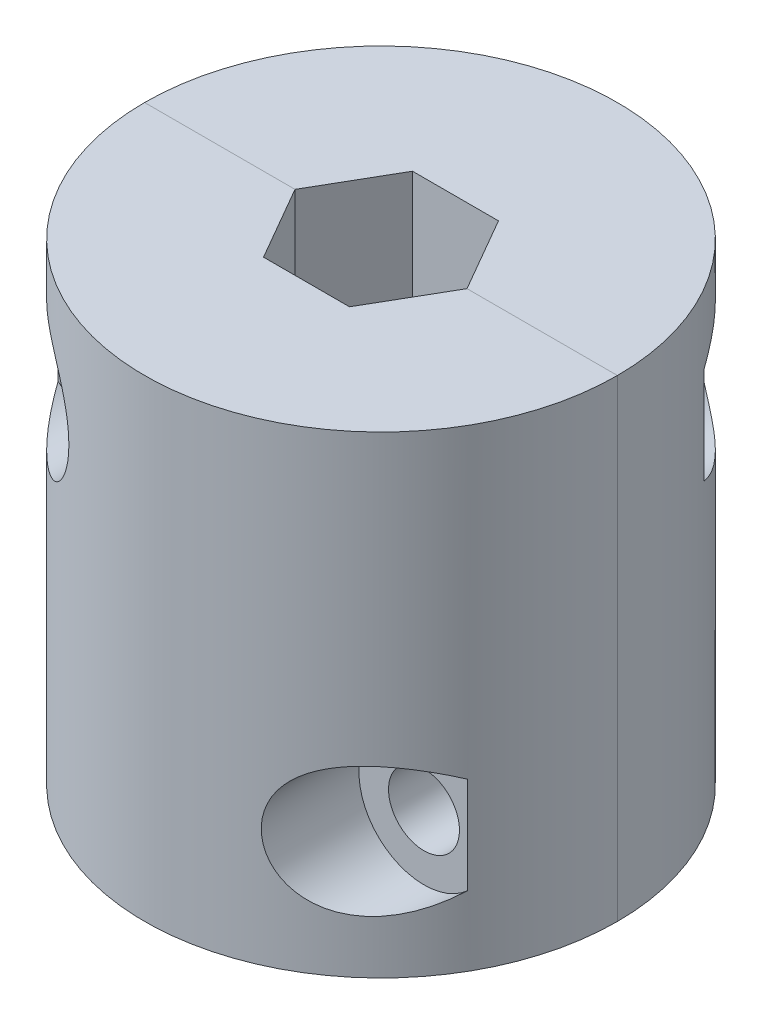
SolidWorks part; units mm, degrees
ref_plane "Front Plane" through (0, 0, 0) normal (0, 0, 1) x (1, 0, 0)
ref_plane "Top Plane" through (0, 0, 0) normal (0, 1, 0) x (1, 0, 0)
ref_plane "Right Plane" through (0, 0, 0) normal (1, 0, 0) x (0, 0, -1)
sketch "Sketch1" plane through (0, 0, 0) normal (0, 1, 0) x (1, 0, 0)
  line L0 (3.6373, 0) -> (10, 0)
  line L1 (-1.8187, -3.15) -> (1.8187, -3.15)
  line L2 (1.8187, -3.15) -> (3.6373, 0)
  line L3 (3.6373, 0) -> (1.8187, 3.15)
  line L4 (1.8187, 3.15) -> (-1.8187, 3.15)
  line L5 (-1.8187, 3.15) -> (-3.6373, 0)
  line L6 (-3.6373, 0) -> (-1.8187, -3.15)
  line L7 (-3.6373, 0) -> (-10, 0)
  line L8 (20, 20) -> (-20, 20)
  line L9 (10, 10) -> (-10, 10)
  line L10 (10, 10) -> (10, -10)
  line L11 (10, -10) -> (-10, -10)
  line L12 (-10, 10) -> (-10, -10)
  line L13 (10, 10) -> (-10, -10) construction
  line L14 (10, -10) -> (-10, 10) construction
  line L15 (-20, 20) -> (-20, -20)
  line L16 (20, -20) -> (-20, -20)
  line L17 (20, 20) -> (20, -20)
  circle A0 centre (0, 0) radius 3.15 construction
  circle A1 centre (0, 0) radius 10
  dimension "D2" = 20
  dimension "D1" = 6.3
  dimension "D3" = 10
extrude "Boss-Extrude1" add sketch "Sketch1" against normal mid plane 20 contours L0 A1 L7 L5 L4 L3 | A1 L10 L9 | A1 L9 L12 region at (0, 0, -4.5935) region at (7.7663, 0, -7.7663) region at (-7.7663, 0, -7.7663)
extrude "Boss-Extrude2" add sketch "Sketch1<3>" along normal mid plane 20 separate body contours L7 A1 L0 L2 L1 L6 | A1 L11 L10 | A1 L12 L11 region at (0, 0, 4.5935) region at (7.7663, 0, 7.7663) region at (-7.7663, 0, 7.7663)
sketch "Sketch1<3>" plane through (0, 0, 0) normal (0, 1, 0) x (1, 0, 0) same geometry as "Sketch1"
sketch "Sketch2" plane through (0, 0, -10) normal (0, 0, -1) x (-1, 0, 0)
  line L0 (-3.6373, 10) -> (-10, 10) construction
  line L1 (-3.6373, 10) -> (-10, 10) construction
  line L2 (-10, -10) -> (-10, 10) construction
  line L3 (0, 0) -> (-10, 0) construction
  line L4 (-10, 0) -> (-10, 10) construction
  line L5 (0, 0) -> (0, -10) construction
  line L6 (-10, -10) -> (10, -10) construction
  circle A0 centre (-6.8187, 5) radius 2.75
  circle A1 centre (-6.8187, 5) radius 1.5
  circle A2 centre (-6.8187, -5) radius 1.5
  circle A3 centre (-6.8187, -5) radius 2.75
  circle A4 centre (6.8187, -5) radius 2.75
  circle A5 centre (6.8187, -5) radius 1.5
  circle A6 centre (6.8187, 5) radius 1.5
  circle A7 centre (6.8187, 5) radius 2.75
  point P7 (-6.8187, 5)
  point P8 (-6.8187, 10)
  point P9 (-10, 5)
  point P13 (-6.8187, -5)
  dimension "D1" = 3
  dimension "D2" = 5.5
extrude "Cut-Extrude4" cut sketch "Sketch2" against normal offset from surface (15 mm away) 5 contours A1 | A5 region at (6.8187, 5, -10) up to face at (6.8187, 0, 0) offset beyond the face yes
extrude "Cut-Extrude10" cut sketch "Sketch2<5>" against normal blind 5 contours A0 A1 | A4 A5 region at (9.4909, 5, -10) region at (-4.1464, -5, -10)
sketch "Sketch2<5>" plane through (0, 0, -10) normal (0, 0, -1) x (-1, 0, 0) same geometry as "Sketch2"
extrude "Cut-Extrude13" cut sketch "Sketch2<9>" along normal blind 15 from surface contours A6 | A2 region at (6.8187, -5, -10) region at (-6.8187, 5, -10) starting at face at (0, 0, 10)
sketch "Sketch2<9>" plane through (0, 0, -10) normal (0, 0, -1) x (-1, 0, 0) same geometry as "Sketch2"
extrude "Cut-Extrude11" cut sketch "Sketch2<6>" along normal blind 5 from surface contours A3 A2 | A7 A6 region at (9.4909, -5, -10) region at (-4.1464, 5, -10) starting at face at (-5.3187, 5, 10)
sketch "Sketch2<6>" plane through (0, 0, -10) normal (0, 0, -1) x (-1, 0, 0) same geometry as "Sketch2"
extrude "Cut-Extrude9" cut sketch "Sketch1<5>" against normal mid plane 20 contours A1 L9 L12 | L17 L8 L15 L16 L12 L9 L10 L11 | A1 L10 L9 | A1 L11 L10 | A1 L12 L11 region at (7.7663, 0, -7.7663) region at (7.7663, 0, 7.7663) region at (-7.7663, 0, -7.7663) region at (-7.7663, 0, 7.7663) region at (19.4343, 0, 0)
sketch "Sketch1<5>" plane through (0, 0, 0) normal (0, 1, 0) x (1, 0, 0) same geometry as "Sketch1"
